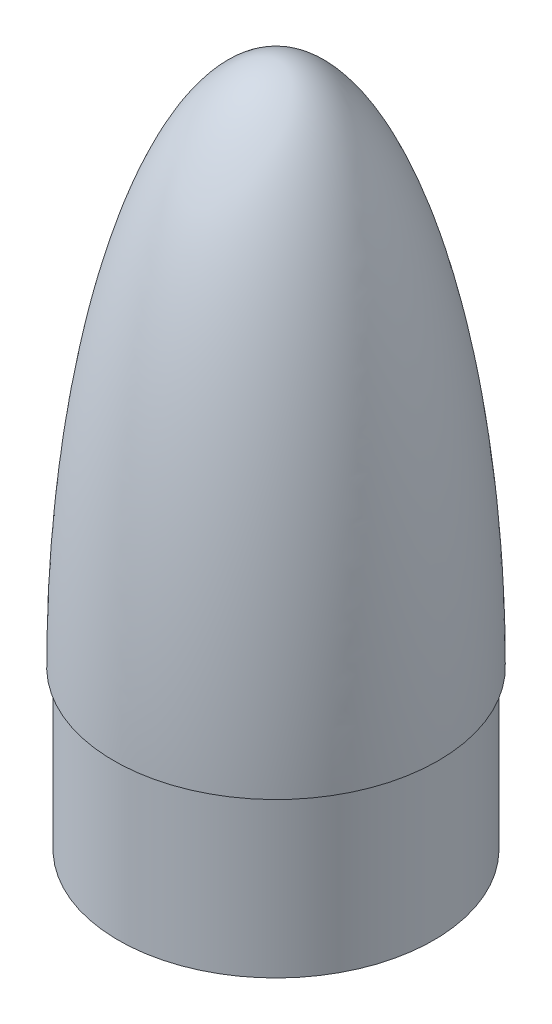
SolidWorks part; units mm, degrees
material "ABS"
ref_plane "Front Plane" through (0, 0, 0) normal (0, 0, 1) x (1, 0, 0)
ref_plane "Top Plane" through (0, 0, 0) normal (0, 1, 0) x (1, 0, 0)
ref_plane "Right Plane" through (0, 0, 0) normal (1, 0, 0) x (0, 0, -1)
sketch "Sketch1" plane through (0, 0, 0) normal (0, 0, 1) x (1, 0, 0)
  line L0 (0, 254) -> (0, 0) construction
  line L1 (78.359, 0) -> (0, 0)
  line L2 (0, 0) -> (0, 254)
  spline S0 degree 4 poles (77.9662, -25.3999) (78.0154, -23.8095) (78.1056, -20.6522) (78.1976, -16.6458) (78.2773, -11.9379) (78.3233, -7.8867) (78.3478, -4.9036) (78.3593, -1.4843) (78.3601, 0.7911) (78.3527, 3.5863) (78.3388, 5.9889) (78.318, 8.3522) (78.2903, 10.7456) (78.247, 13.7314) (78.1811, 17.3117) (78.0839, 21.4904) (77.9448, 26.2641) (77.7777, 31.0376) (77.5823, 35.8096) (77.3585, 40.5805) (77.0429, 46.5423) (76.6791, 52.5014) (76.2664, 58.4574) (75.8041, 64.4096) (75.404, 69.1689) (74.8656, 75.1148) (74.1574, 82.244) (73.2383, 90.5517) (72.0557, 100.0308) (70.7355, 109.4917) (69.2709, 118.9313) (67.25, 130.6999) (64.5017, 144.7638) (61.3086, 158.736) (57.591, 172.5772) (53.383, 186.2759) (49.2387, 198.0448) (44.4832, 209.5873) (38.9429, 220.7192) (34.2562, 228.6936) (29.8187, 235.0954) (25.6242, 240.1829) (21.9789, 243.9262) (18.5702, 246.8595) (15.4743, 249.0762) (12.5634, 250.7857) (9.7723, 252.0835) (7.0631, 253.0286) (4.2754, 253.6868) (2.188, 253.9399) (0.7672, 253.9999) (0, 254) knots 0 0 0 0 0 0.020823 0.041645 0.052056 0.062468 0.072879 0.08329 0.09112 0.098949 0.106779 0.114608 0.122438 0.130267 0.145926 0.161585 0.177244 0.192903 0.208562 0.224221 0.23988 0.271198 0.286857 0.302516 0.318175 0.333834 0.365152 0.39647 0.427788 0.459106 0.490424 0.521742 0.584379 0.647015 0.678333 0.709651 0.772287 0.810589 0.841907 0.872608 0.893486 0.912628 0.928287 0.941045 0.952387 0.962498 0.972496 0.981349 0.98995 1 1 1 1 1 construction
  spline S1 degree 4 poles (78.359, 0) (78.359, 0.5473) (78.3578, 1.6496) (78.3527, 3.5863) (78.3388, 5.9889) (78.318, 8.3522) (78.2903, 10.7456) (78.247, 13.7314) (78.1811, 17.3117) (78.0839, 21.4904) (77.9448, 26.2641) (77.7777, 31.0376) (77.5823, 35.8096) (77.3585, 40.5805) (77.0429, 46.5423) (76.6791, 52.5014) (76.2664, 58.4574) (75.8041, 64.4096) (75.404, 69.1689) (74.8656, 75.1148) (74.1574, 82.244) (73.2383, 90.5517) (72.0557, 100.0308) (70.7355, 109.4917) (69.2709, 118.9313) (67.25, 130.6999) (64.5017, 144.7638) (61.3086, 158.736) (57.591, 172.5772) (53.383, 186.2759) (49.2387, 198.0448) (44.4832, 209.5873) (38.9429, 220.7192) (34.2562, 228.6936) (29.8187, 235.0954) (25.6242, 240.1829) (21.9789, 243.9262) (18.5702, 246.8595) (15.4743, 249.0762) (12.5634, 250.7857) (9.7723, 252.0835) (7.0631, 253.0286) (4.2754, 253.6868) (2.188, 253.9399) (0.7672, 253.9999) (0, 254) knots 0.08329 0.08329 0.08329 0.08329 0.08329 0.09112 0.098949 0.106779 0.114608 0.122438 0.130267 0.145926 0.161585 0.177244 0.192903 0.208562 0.224221 0.23988 0.271198 0.286857 0.302516 0.318175 0.333834 0.365152 0.39647 0.427788 0.459106 0.490424 0.521742 0.584379 0.647015 0.678333 0.709651 0.772287 0.810589 0.841907 0.872608 0.893486 0.912628 0.928287 0.941045 0.952387 0.962498 0.972496 0.981349 0.98995 1 1 1 1 1
revolve "Revolve1" add sketch "Sketch1" angle 360 about L0
sketch "Sketch2" plane through (0, 0, 0) normal (0, -1, 0) x (1, 0, 0)
  circle A0 centre (0, 0) radius 76.2
extrude "Boss-Extrude1" add sketch "Sketch2" along normal blind 76.2
ref_axis "Axis1" through (0, 270.51, 0) along (0, -1, 0)
sketch "Sketch21" plane through (0, -76.2, 0) normal (0, -1, 0) x (1, 0, 0)
  line L1 (-25.4, 25.4) -> (25.4, 25.4) construction
  line L2 (-25.4, 25.4) -> (-25.4, -25.4) construction
  line L3 (-25.4, -25.4) -> (25.4, -25.4) construction
  line L4 (25.4, 25.4) -> (25.4, -25.4) construction
  circle A0 centre (-37.813, 0) radius 2.6035
  circle A1 centre (0, 37.813) radius 2.6035
  circle A2 centre (37.813, 0) radius 2.6035
  circle A3 centre (0, -37.813) radius 2.6035
  point P12 (-25.4, 0)
  point P14 (25.4, 0)
  point P15 (0, 25.4)
  dimension "D1" = 50.8
  dimension "D3" = 5.207
  dimension "D5" = 12.413
  dimension "D8" = 5.207
  dimension "D9" = 5.207
  dimension "D10" = 5.207
  dimension "D2" = 50.8
  dimension "D4" = 12.413
  dimension "D6" = 12.413
  dimension "D7" = 12.413
extrude "Cut-Extrude4" cut sketch "Sketch21" against normal blind 9.525
sketch "Sketch22" plane through (0, -76.2, 0) normal (0, -1, 0) x (1, 0, 0)
  line L0 (-71.842, 0) -> (0, 71.842) construction
  line L1 (0, 71.842) -> (71.842, 0) construction
  line L2 (71.842, 0) -> (0, -71.842) construction
  line L3 (0, -71.842) -> (-71.842, 0) construction
  line L4 (0, -37.813) -> (37.813, 0) construction
  circle A0 centre (-35.921, -35.921) radius 2.6035
  circle A1 centre (-35.921, 35.921) radius 2.6035
  circle A2 centre (35.921, 35.921) radius 2.6035
  circle A3 centre (35.921, -35.921) radius 2.6035
  dimension "D6" = 5.207
  dimension "D7" = 5.207
  dimension "D8" = 5.207
  dimension "D9" = 5.207
  dimension "D1" = 101.6
  dimension "D2" = 101.6
  dimension "D3" = 50.8
  dimension "D4" = 50.8
  dimension "D5" = 90
extrude "Cut-Extrude5" cut sketch "Sketch22" against normal blind 9.525
sketch "Sketch3" plane through (0, 0, 0) normal (0, 0, 1) x (1, 0, 0)
  line L0 (0, 0) -> (50.6956, 0)
  line L1 (-76.2, 0) -> (76.2, 0) construction
  line L2 (0, 0) -> (0, 122.511)
  line L3 (0, 270.51) -> (0, -92.71) construction
  arc A0 (50.6956, 0) -> (0, 122.511) centre (-122.6821, 0) ccw
revolve "Cut-Revolve1" [suppressed] cut sketch "Sketch3" angle 360 about axis through (0, 270.51, 0) along (0, -1, 0)
sketch "Sketch23" plane through (0, 0, 0) normal (1, 0, 0) x (0, 0, -1)
  line L0 (0, 0) -> (0, 50.8) construction
  line L1 (22.6462, 0) -> (22.6462, 41.91) construction
  dimension "D1" = 50.8
  dimension "D2" = 41.91
sketch "Sketch26" plane through (0, 0, 0) normal (0, 0, 1) x (1, 0, 0)
  line L0 (-41.2191, 0) -> (-41.2191, 50.8) construction
  line L1 (-76.2, 0) -> (76.2, 0) construction
  dimension "D1" = 50.8
ref_plane "Plane6" through (0, 44.0168, -17.2793) normal (0, -0.9308, 0.3654) x (-1, 0, 0)
sketch "Sketch27" plane through (0, 44.0168, -17.2793) normal (0, -0.9308, 0.3654) x (-1, 0, 0)
  line L1 (-45.4713, 10.0087) -> (-7.3713, 10.0087)
  line L2 (-45.4713, 10.0087) -> (-45.4713, -28.0913)
  line L3 (-45.4713, -28.0913) -> (-7.3713, -28.0913)
  line L4 (-7.3713, 10.0087) -> (-7.3713, -28.0913)
  line L5 (18.1695, 10.7171) -> (56.2695, 10.7171)
  line L6 (18.1695, 10.7171) -> (18.1695, -27.3829)
  line L7 (18.1695, -27.3829) -> (56.2695, -27.3829)
  line L8 (56.2695, 10.7171) -> (56.2695, -27.3829)
  line L9 (-42.6983, -37.5285) -> (-4.5983, -37.5285)
  line L10 (-42.6983, -37.5285) -> (-42.6983, -75.6285)
  line L11 (-42.6983, -75.6285) -> (-4.5983, -75.6285)
  line L12 (-4.5983, -37.5285) -> (-4.5983, -75.6285)
  line L13 (5.5532, -38.7968) -> (43.6532, -38.7968)
  line L14 (5.5532, -38.7968) -> (5.5532, -76.8968)
  line L15 (5.5532, -76.8968) -> (43.6532, -76.8968)
  line L16 (43.6532, -38.7968) -> (43.6532, -76.8968)
  dimension "D1" = 38.1
  dimension "D2" = 38.1
  dimension "D3" = 38.1
  dimension "D4" = 38.1
  dimension "D5" = 38.1
  dimension "D6" = 38.1
  dimension "D7" = 38.1
  dimension "D8" = 38.1
extrude "Cut-Extrude7" cut sketch "Sketch27" against normal blind 50.8
ref_plane "Plane7" through (0, 20.3734, -7.9978) normal (0, -0.9308, 0.3654) x (-1, 0, 0)
sketch "Sketch28" plane through (0, 20.3734, -7.9978) normal (0, -0.9308, 0.3654) x (-1, 0, 0)
  line L1 (-41.6572, 47.5838) -> (-3.5572, 47.5838)
  line L2 (-41.6572, 47.5838) -> (-41.6572, 9.4838)
  line L3 (-41.6572, 9.4838) -> (-3.5572, 9.4838)
  line L4 (-3.5572, 47.5838) -> (-3.5572, 9.4838)
  line L5 (14.4454, 31.7478) -> (52.5454, 31.7478)
  line L6 (14.4454, 31.7478) -> (14.4454, -6.3522)
  line L7 (14.4454, -6.3522) -> (52.5454, -6.3522)
  line L8 (52.5454, 31.7478) -> (52.5454, -6.3522)
  line L9 (-46.6983, -8.4512) -> (-8.5983, -8.4512)
  line L10 (-46.6983, -8.4512) -> (-46.6983, -46.5512)
  line L11 (-46.6983, -46.5512) -> (-8.5983, -46.5512)
  line L12 (-8.5983, -8.4512) -> (-8.5983, -46.5512)
  line L13 (2.8181, -17.3185) -> (40.9181, -17.3185)
  line L14 (2.8181, -17.3185) -> (2.8181, -55.4185)
  line L15 (2.8181, -55.4185) -> (40.9181, -55.4185)
  line L16 (40.9181, -17.3185) -> (40.9181, -55.4185)
  dimension "D1" = 38.1
  dimension "D2" = 38.1
  dimension "D3" = 38.1
  dimension "D4" = 38.1
  dimension "D5" = 38.1
  dimension "D6" = 38.1
  dimension "D7" = 38.1
  dimension "D8" = 38.1
extrude "Cut-Extrude8" cut sketch "Sketch28" against normal blind 12.7 and the other way blind 12.7
ref_plane "Plane8" through (0, 109.0364, -42.8034) normal (0, -0.9308, 0.3654) x (-1, 0, 0)
sketch "Sketch29" plane through (0, 109.0364, -42.8034) normal (0, -0.9308, 0.3654) x (-1, 0, 0)
  line L1 (-30.2108, -33.6789) -> (20.5892, -33.6789)
  line L2 (-30.2108, -33.6789) -> (-30.2108, -84.4789)
  line L3 (-30.2108, -84.4789) -> (20.5892, -84.4789)
  line L4 (20.5892, -33.6789) -> (20.5892, -84.4789)
  dimension "D1" = 50.8
  dimension "D2" = 50.8
extrude "Cut-Extrude9" cut sketch "Sketch29" against normal blind 63.5
sketch "Sketch30" plane through (0, -76.2, 0) normal (0, -1, 0) x (1, 0, 0)
  circle A0 centre (0, 0) radius 9.525
  dimension "D1" = 19.05
extrude "Cut-Extrude10" cut sketch "Sketch30" against normal blind 19.05
equation "\"Bodytube_OD\"= 6.17in"
equation "\"Bodytube_ID\"= 5.998in"
equation "\"R\"= \"Bodytube_ID\" / 2"
equation "\"L\"= 30in"
